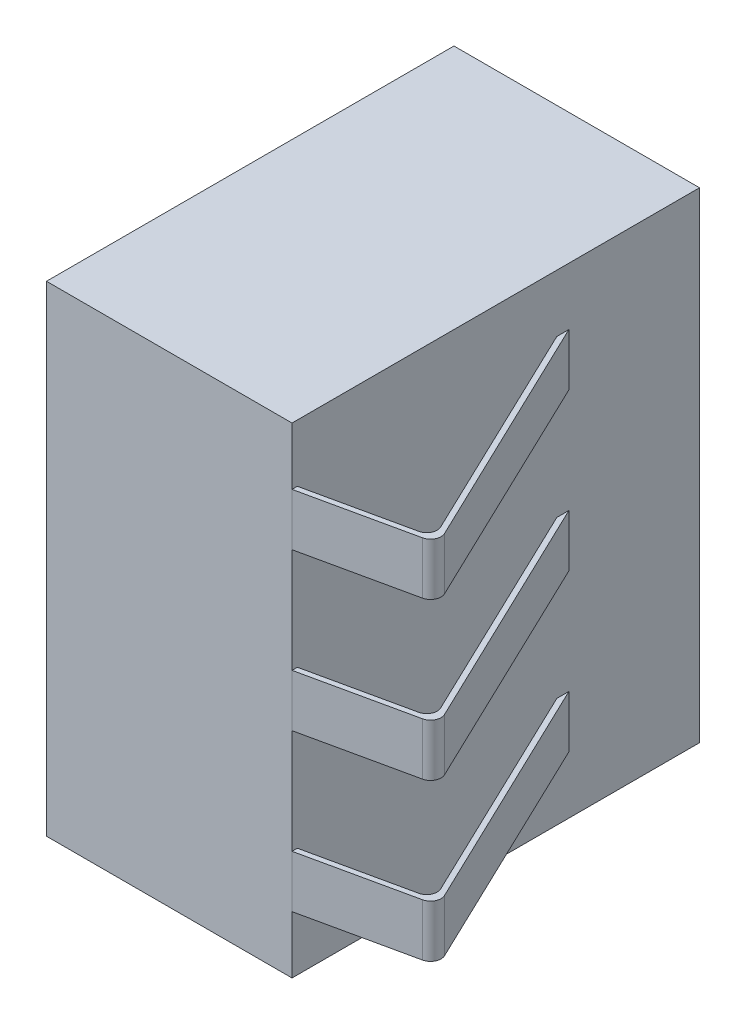
SolidWorks part; units mm, degrees
ref_plane "Front Plane" through (0, 0, 0) normal (0, 0, 1) x (1, 0, 0)
ref_plane "Top Plane" through (0, 0, 0) normal (0, 1, 0) x (1, 0, 0)
ref_plane "Right Plane" through (0, 0, 0) normal (1, 0, 0) x (0, 0, -1)
sketch "Sketch1" plane through (0, 0, 0) normal (0, 0, 1) x (1, 0, 0)
  line L1 (-2.35, -4.6) -> (2.35, -4.6)
  line L2 (-2.35, -4.6) -> (-2.35, 4.6)
  line L3 (-2.35, 4.6) -> (2.35, 4.6)
  line L4 (2.35, -4.6) -> (2.35, 4.6)
  line L5 (-2.35, -4.6) -> (2.35, 4.6) construction
  line L6 (-2.35, 4.6) -> (2.35, -4.6) construction
  point P0 (0, 0)
  dimension "D1" = 4.7
  dimension "D2" = 9.2
extrude "Boss-Extrude1" add sketch "Sketch1" along normal blind 7.8
sketch "Sketch2" plane through (0, 0, 0) normal (0, 1, 0) x (1, 0, 0)
  line L0 (2.35, -7.8) -> (4.65, -7.3)
  line L1 (2.35, -7.8) -> (2.35, 0) construction
  line L2 (4.65, -7.3) -> (2.35, -2.5)
  line L3 (2.35, -2.5) -> (2.35, -2.7314)
  line L4 (2.35, -2.7314) -> (4.5052, -7.2292)
  line L5 (4.5052, -7.2292) -> (2.35, -7.6977)
  line L6 (2.35, -7.6977) -> (2.35, -7.8)
  line L7 (4.5052, -7.2292) -> (4.5953, -7.1859) construction
  line L8 (4.5052, -7.2292) -> (4.5264, -7.3269) construction
  line L10 (2.35, 0) -> (-2.35, 0) construction
  line L11 (-2.35, -7.8) -> (-2.35, 0) construction
  line L12 (2.35, -7.8) -> (-2.35, -7.8) construction
  dimension "D1" = 0.1
  dimension "D2" = 2.5
  dimension "D3" = 7
  dimension "D4" = 0.5
extrude "Boss-Extrude2" add sketch "Sketch2" along normal mid plane 1
fillet "Fillet1" radius 0.2 1 edges at (4.5052, 0, 7.2292)
fillet "Fillet2" radius 0.2 1 edges at (4.65, 0, 7.3)
pattern_linear "LPattern2" count 2 spacing 3 along (0, -1, 0) count 2 spacing 3 along (0, 1, 0) of "Boss-Extrude2", "Fillet1", "Fillet2" pattern seed only yes
